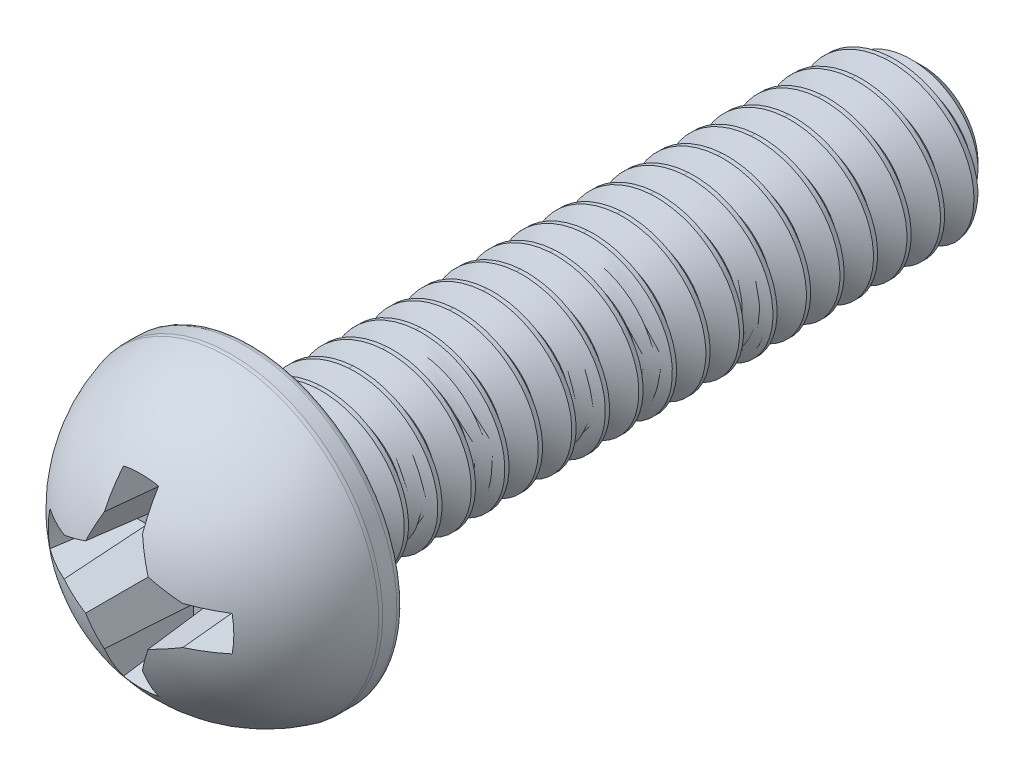
SolidWorks part; units mm, degrees
ref_plane "Front" through (0, 0, 0) normal (0, 0, 1) x (1, 0, 0)
ref_plane "Top" through (0, 0, 0) normal (0, 1, 0) x (1, 0, 0)
ref_plane "Right" through (0, 0, 0) normal (1, 0, 0) x (0, 0, -1)
sketch "Sketch1" plane through (0, 0, 0) normal (0, 0, 1) x (1, 0, 0)
  circle A0 centre (0, 0) radius 1.4351
  dimension "Head Dia" = 2.8702
extrude "Extrude3" add sketch "Sketch1" along normal blind 1.3462
sketch "Sketch11" plane through (0, 0, 0) normal (1, 0, 0) x (0, 0, -1)
  line L0 (0, 0) -> (-1.6002, 0) construction
  line L4 (-1.3462, 1.4351) -> (-1.3462, -1.4351) construction
  line L5 (-1.6002, 1.6548) -> (0, 1.6548)
  line L7 (0, 1.6548) -> (0, 1.3678)
  line L8 (-0.2019, 1.4351) -> (-0.0673, 1.4351)
  line L9 (0, -1.4351) -> (0, 1.4351) construction
  line L11 (0, 1.4351) -> (-1.3462, 1.4351) construction
  line L13 (-1.3462, 0) -> (-1.6002, 0)
  line L14 (-1.6002, 0) -> (-1.6002, 1.6548)
  arc A0 (-0.2353, 1.4309) -> (-1.3462, 0) centre (0.1308, 0) ccw
  arc A1 (-0.0673, 1.4351) -> (0, 1.3678) centre (-0.0673, 1.3678) cw
  arc A2 (-0.2353, 1.4309) -> (-0.2019, 1.4351) centre (-0.2019, 1.3005) cw
  dimension "D2" = 0.0673
  dimension "D4" = 0.1346
  dimension "D1" = 0.1346
  dimension "D3" = 0.254
  dimension "D5" = 0.287
revolve "Cut-Revolve3" cut sketch "Sketch11" angle 360 about L0
sketch "Sketch4" plane through (0, 0, 0) normal (1, 0, 0) x (0, 0, -1)
  line L0 (0, 0) -> (6.35, 0)
  line L3 (6.35, 0) -> (6.35, 0.762)
  line L4 (6.35, 0.762) -> (0, 0.762)
  line L6 (0, 0.762) -> (0, 0)
  line L9 (6.35, 0.762) -> (6.35, -0.762) construction
  dimension "dia" = 1.524
  dimension "length" = 6.35
revolve "Revolve1" add sketch "Sketch4" angle 360 about L0
chamfer "Chamfer1" distance 0.2381 angle 45 1 edges at (0.762, 0, -6.35)
sketch "Sketch13" plane through (0, 0, -6.35) normal (0, 0, -1) x (-1, 0, 0)
  circle A2 centre (0, 0) radius 0.762
curve "Helix/Spiral1" pitch 0.3175 height 6.6675 turns 21
sketch "Sketch14" plane through (0, 0, 0) normal (1, 0, 0) x (0, 0, -1)
  line L0 (6.35, 0.762) -> (6.6278, 0.762)
  line L1 (6.6278, 0.762) -> (6.5088, 0.5472)
  line L2 (6.5088, 0.5472) -> (6.4691, 0.5472)
  line L3 (6.4691, 0.5472) -> (6.35, 0.762)
  line L4 (6.4095, 0.6546) -> (6.5683, 0.6546) construction
  dimension "D1" = 0.0397
  dimension "D2" = 58
  dimension "D3" = 0.1588
sweep "Cut-Sweep1" cut profiles "Sketch14" path "Helix/Spiral1"
ref_plane "Plane1" through (0, 0, 31.75) normal (0, 0, -1) x (-1, 0, 0)
sketch "Sketch22" plane through (0, 0, 0) normal (0, 1, 0) x (1, 0, 0)
  line L0 (0, 6.35) -> (0, 0) construction
  line L1 (0, 6.35) -> (0, 0)
split line "Split Line1"
sketch "Sketch29" [suppressed] plane through (0, 0, -12.7) normal (0, 0, -1) x (-1, 0, 0)
  circle A0 centre (0, 0) radius 4.7625 construction
  circle A1 centre (0, 0) radius 4.7625
  point P3 (0, -4.7625)
extrude "Extrude11" [suppressed] add sketch "Sketch29" against normal up to surface (12.7 mm away)
sketch "Sketch26" plane through (0, 0, 0) normal (0, 0, 1) x (1, 0, 0)
  circle A1 centre (0, 0) radius 0.5461
  dimension "D1" = 1.0922
extrude "Extrude12" add sketch "Sketch26" along normal up to vertex (0.2353 mm away) up to point (0, 1.4309, 0.2353)
ref_plane "Plane2" through (0, 0, 1.3462) normal (0, 0, 1) x (1, 0, 0)
sketch "Sketch12" plane through (0, 0, 1.3462) normal (0, 0, 1) x (1, 0, 0)
  line L0 (0, 0) -> (0.1913, 0.1913) construction
  line L1 (0, 0) -> (0, -0.5959) construction
  line L2 (0.9374, 0.1913) -> (0.5644, 0.1913)
  line L3 (0, 0.9567) -> (0, 1.4351) construction
  line L8 (0.1913, 0.5644) -> (0.1913, 0.9374)
  line L9 (0.1913, 0.1913) -> (0.5644, 0.5644) construction
  line L10 (0.5644, 0.1913) -> (0.3006, 0.3006)
  line L11 (0.3006, 0.3006) -> (0.1913, 0.5644)
  line L12 (0.5644, 0.1913) -> (0.1913, 0.1913) construction
  line L13 (0.1913, 0.5644) -> (0.1913, 0.1913) construction
  line L14 (0, 0) -> (0, 0.9567)
  line L15 (0, 0) -> (0.9567, 0)
  circle A1 centre (0, 0) radius 1.4351 construction
  arc A2 (0.9567, 0) -> (0.9374, 0.1913) centre (0, 0) ccw
  arc A3 (0.1913, 0.9374) -> (0, 0.9567) centre (0, 0) ccw
  circle A5 centre (0, 0) radius 0.5959 construction
  arc A6 (0.5644, 0.1913) -> (0.1913, 0.5644) centre (0.5644, 0.5644) cw construction
  dimension "D1" = 0.4784
  dimension "Phillips Dia" = 1.9135
  dimension "Phillips Width" = 0.3827
extrude "Cut-Extrude3" cut sketch "Sketch12" against normal blind 0.8975
pattern_circular "CirPattern1" count 4 over 360 about axis through (0, 0, 0) along (0, 0, 1) of "Cut-Extrude3"
draft "Draft1" type of draft neutral plane draft angle 15 neutral plane "Plane2" faces to draft 4 face at (-0.9471, 0, 0.7216) face at (0, -0.9471, 0.7216) face at (0.9471, 0, 0.7216) face at (0, 0.9471, 0.7216) neutral plane through (0, 0, 1.3462) neutral plane normal (0, 0, 1) parameters "D1"=15
draft "Draft2" type of draft neutral plane draft angle 5 neutral plane "Plane2" faces to draft 16 face at (0.1913, 0.6494, 0.7198) face at (0.2458, 0.4329, 0.8523) face at (0.4329, 0.2458, 0.8523) face at (0.6494, 0.1913, 0.7198) face at (0.6494, -0.1913, 0.7198) face at (0.4329, -0.2458, 0.8523) face at (0.2458, -0.4329, 0.8523) face at (0.1913, -0.6494, 0.7198) face at (-0.1913, -0.6494, 0.7198) face at (-0.2458, -0.4329, 0.8523) face at (-0.4329, -0.2458, 0.8523) face at (-0.6494, -0.1913, 0.7198) face at (-0.6494, 0.1913, 0.7198) face at (-0.4329, 0.2458, 0.8523) face at (-0.2458, 0.4329, 0.8523) face at (-0.1913, 0.6494, 0.7198) neutral plane through (0, 0, 1.3462) neutral plane normal (0, 0, 1) parameters "D1"=5
sketch "Sketch18" plane through (0, 0, 0) normal (1, 0, 0) x (0, 0, -1)
  line L1 (6.35, 0.762) -> (0, 0.762) construction
  point P0 (4.445, -0.762)
  point P1 (4.445, 0.762)
  point P2 (-1.3462, 0.3006)
  dimension "D1" = 1.905
equation "\"Phillips Dia@Sketch12\"=\"Head Dia@Sketch1\"/1.5"
equation "\"Phillips Width@Sketch12\"=\"Phillips Dia@Sketch12\"/5"
equation "\"Phillips Depth@Cut-Extrude3\"= \"Head Ht@Extrude3\" / 1.5"
equation "\"D3@Helix/Spiral1\" = \"Length@Sketch4\" + \"D4@Helix/Spiral1\""
equation "\"D1@Sketch14\" = \"D4@Helix/Spiral1\" * .125"
equation "\"D3@Sketch14\" = \"D4@Helix/Spiral1\" * .5"
equation "\"D1@Sketch11\" = \"Head Ht@Extrude3\" / 10"
equation "\"D2@Sketch11\" = \"D1@Sketch11\" / 2"
equation "\"D4@Sketch11\" = \"D1@Sketch11\""
equation "\"D5@Sketch11\" = \"Head Dia@Sketch1\" / 10"
equation "\"D1@Chamfer1\" = \"D4@Helix/Spiral1\" * .75"
